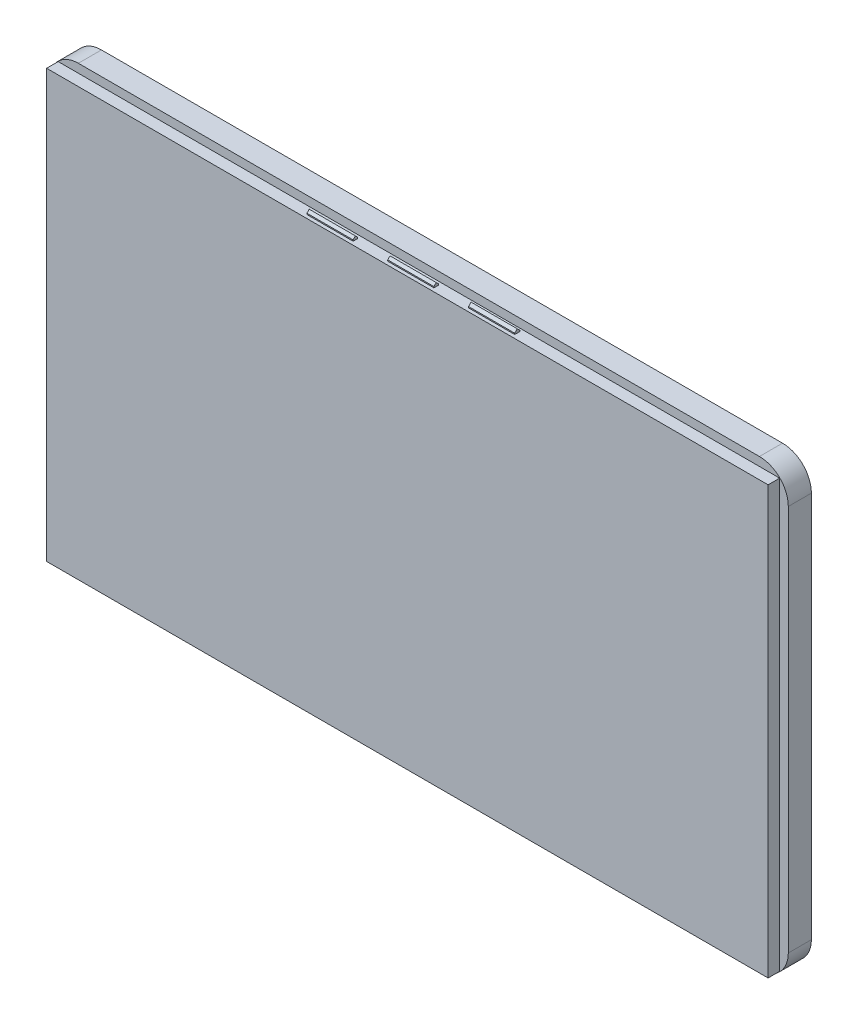
SolidWorks part; units mm, degrees
ref_plane "Front Plane" through (0, 0, 0) normal (0, 0, 1) x (1, 0, 0)
ref_plane "Top Plane" through (0, 0, 0) normal (0, 1, 0) x (1, 0, 0)
ref_plane "Right Plane" through (0, 0, 0) normal (1, 0, 0) x (0, 0, -1)
sketch "Sketch1" plane through (0, 0, 0) normal (0, 0, 1) x (1, 0, 0)
  line L1 (0, 0) -> (64, 0)
  line L2 (0, 0) -> (0, 38.5)
  line L3 (0, 38.5) -> (64, 38.5)
  line L4 (64, 0) -> (64, 38.5)
  dimension "D1" = 64
  dimension "D2" = 38.5
extrude "Boss-Extrude1" add sketch "Sketch1" along normal blind 3
sketch "Sketch2" plane through (0, 0, 3) normal (0, 0, 1) x (1, 0, 0)
  line L0 (64, 0) -> (64, 38.5) construction
  line L1 (0, 38.5) -> (64, 38.5)
  line L2 (0, 38.5) -> (0, 37.75)
  line L3 (0, 37.75) -> (64, 37.75)
  line L4 (64, 38.5) -> (64, 37.75)
  line L5 (64, 38.5) -> (0, 38.5) construction
  line L6 (0, 0) -> (64, 0) construction
  line L7 (0, 0.75) -> (64, 0.75)
  line L8 (0, 0.75) -> (0, 0)
  line L9 (0, 0) -> (64, 0)
  line L10 (64, 0.75) -> (64, 0)
  line L11 (0, 38.5) -> (0, 0) construction
  line L12 (0, 38.5) -> (0.75, 38.5)
  line L13 (0, 38.5) -> (0, 0)
  line L14 (0, 0) -> (0.75, 0)
  line L15 (0.75, 38.5) -> (0.75, 0)
  line L17 (63.25, 38.5) -> (64, 38.5)
  line L18 (63.25, 38.5) -> (63.25, 0)
  line L19 (63.25, 0) -> (64, 0)
  line L20 (64, 38.5) -> (64, 0)
  line M14 (64, 0) -> (64, 38.5)
  line M15 (64, 38.5) -> (0, 38.5)
  dimension "D1" = 64
  dimension "D2" = 0
  dimension "D3" = 0.75
  dimension "D4" = 0
  dimension "D5" = 64
  dimension "D6" = 0
  dimension "D7" = 0.75
  dimension "D8" = 0
  dimension "D9" = 0
  dimension "D10" = 0.75
  dimension "D11" = 38.5
  dimension "D12" = 0.75
  dimension "D13" = 0
  dimension "D14" = 38.5
  dimension "D15" = 0
extrude "Cut-Extrude1" cut sketch "Sketch2" against normal blind 1 contours L18 L1 L15 L3 | L18 L3 M15 M14 | L3 L18 L7 M14 | L7 L10 L9 L8 | L13 L14 L15 L12 region at (32, 38.125, 3) region at (63.625, 38.125, 3) region at (63.625, 19.25, 3)
sketch "Sketch3" plane through (0, 0.75, 0) normal (0, -1, 0) x (1, 0, 0)
  line L0 (0.75, 3) -> (63.25, 3) construction
  line L1 (30, 2.7) -> (34, 2.7)
  line L2 (30, 2.7) -> (30, 2.3)
  line L3 (30, 2.3) -> (34, 2.3)
  line L4 (34, 2.7) -> (34, 2.3)
  line L6 (63.25, 2) -> (63.25, 3) construction
  line L7 (0.75, 3) -> (0.75, 2) construction
  line L9 (37, 2.7) -> (41, 2.7)
  line L10 (37, 2.7) -> (37, 2.2592)
  line L11 (37, 2.2592) -> (41, 2.2592)
  line L12 (41, 2.7) -> (41, 2.2592)
  line L13 (27, 2.7) -> (23, 2.7)
  line L14 (27, 2.7) -> (27, 2.3)
  line L15 (27, 2.3) -> (23, 2.3)
  line L16 (23, 2.7) -> (23, 2.3)
  dimension "D1" = 0.3
  dimension "D2" = 4
  dimension "D3" = 4
  dimension "D4" = 29.25
  dimension "D5" = 29.25
  dimension "D6" = 3
  dimension "D7" = 3
  dimension "D8" = 4
  dimension "D9" = 0.4
extrude "Boss-Extrude2" add sketch "Sketch3" against normal blind 37.5 and the other way blind 0.5
chamfer "Chamfer8" distance 0.4 2 edges at (39, 0.25, 2.2592) (39, 0.25, 2.7)
chamfer "Chamfer9" distance 0.4 angle 45 2 edges at (32, 0.25, 2.3) (32, 0.25, 2.7)
chamfer "Chamfer10" distance 0.4 angle 45 2 edges at (25, 0.25, 2.3) (25, 0.25, 2.7)
chamfer "Chamfer11" distance 0.4 angle 45 6 edges at (39, 38.25, 2.2592) (39, 38.25, 2.7) (32, 38.25, 2.3) (32, 38.25, 2.7) (25, 38.25, 2.3) (25, 38.25, 2.7)
fillet "Fillet7" radius 2.5 4 edges at (0, 0, 1) (64, 0, 1) (64, 38.5, 1) (0, 38.5, 1)
